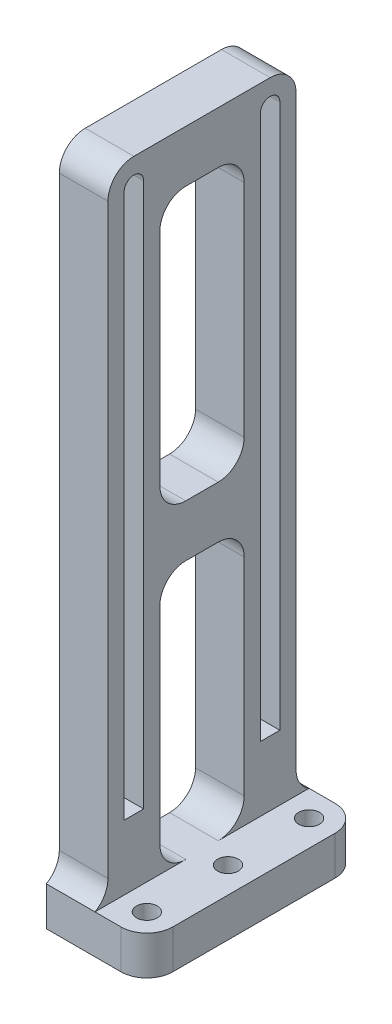
SolidWorks part; units mm, degrees
ref_plane "Front Plane" through (0, 0, 0) normal (0, 0, 1) x (1, 0, 0)
ref_plane "Top Plane" through (0, 0, 0) normal (0, 1, 0) x (1, 0, 0)
ref_plane "Right Plane" through (0, 0, 0) normal (1, 0, 0) x (0, 0, -1)
sketch "Sketch1" plane through (0, 0, 0) normal (0, 1, 0) x (1, 0, 0)
  line L0 (0, -12.5) -> (0, 12.5) construction
  line L1 (-4, -12.5) -> (-4, 12.5)
  line L2 (4, -12.5) -> (4, 12.5)
  line L3 (0, 16.5) -> (-4, 16.5)
  line L4 (-4, 16.5) -> (-4, 12.5)
  line L5 (-4, -12.5) -> (-4, -16.5)
  line L6 (-4, -16.5) -> (0, -16.5)
  arc A0 (-4, -12.5) -> (4, -12.5) centre (0, -12.5) ccw
  arc A1 (4, 12.5) -> (-4, 12.5) centre (0, 12.5) ccw
  circle A2 centre (0, -12.5) radius 1.6
  circle A3 centre (0, 0) radius 1.6
  circle A4 centre (0, 12.5) radius 1.6
  point P2 (0, 0)
  dimension "D2" = 3.2
  dimension "D1" = 25
  dimension "D3" = 8
extrude "Boss-Extrude1" add sketch "Sketch1" along normal blind 6
sketch "Sketch2" plane through (-4, 0, 0) normal (-1, 0, 0) x (0, 0, 1)
  line L0 (0, 0) -> (0, 99.754) construction
  line L1 (-16.5, 0) -> (16.5, 0) construction
  line L2 (0, 49.877) -> (-10.5, 49.877) construction
  line L3 (-10.5, -0.123) -> (-10.5, 99.877) construction
  line L4 (-14.5, -0.123) -> (-14.5, 99.877)
  line L5 (-6.5, -0.123) -> (-6.5, 99.877)
  line L6 (10.5, 99.877) -> (-10.5, 99.877) construction
  line L7 (-12, -0.123) -> (-12, 99.877)
  line L8 (-9, -0.123) -> (-9, 99.877)
  line L9 (10.5, 95.877) -> (-10.5, 95.877)
  line L10 (10.5, 49.877) -> (-10.5, 49.877) construction
  line L11 (9, -0.123) -> (9, 99.877)
  line L12 (12, -0.123) -> (12, 99.877)
  line L13 (10.5, -0.123) -> (10.5, 99.877) construction
  line L14 (14.5, -0.123) -> (14.5, 99.877)
  line L15 (6.5, -0.123) -> (6.5, 99.877)
  line L16 (10.5, 103.877) -> (-10.5, 103.877)
  line L17 (10.5, 45.877) -> (-10.5, 45.877)
  line L18 (-16.5, 0) -> (16.5, 0)
  line L19 (16.5, 0) -> (16.5, 6)
  line L20 (16.5, 6) -> (-16.5, 6)
  line L21 (-16.5, 6) -> (-16.5, 0)
  line L22 (-16.5, 0) -> (16.5, 0)
  line L23 (16.5, 0) -> (16.5, 6)
  line L24 (16.5, 6) -> (-16.5, 6)
  line L25 (-16.5, 6) -> (-16.5, 0)
  line L26 (10.5, 53.877) -> (-10.5, 53.877)
  line L27 (-12, 16) -> (-9, 16)
  line L28 (12, 16) -> (9, 16)
  arc A0 (-14.5, -0.123) -> (-6.5, -0.123) centre (-10.5, -0.123) ccw
  arc A1 (-6.5, 99.877) -> (-14.5, 99.877) centre (-10.5, 99.877) ccw
  arc A2 (-9, 99.877) -> (-12, 99.877) centre (-10.5, 99.877) ccw
  arc A3 (-12, -0.123) -> (-9, -0.123) centre (-10.5, -0.123) ccw
  arc A4 (9, 99.877) -> (12, 99.877) centre (10.5, 99.877) cw
  arc A5 (12, -0.123) -> (9, -0.123) centre (10.5, -0.123) cw
  arc A6 (14.5, -0.123) -> (6.5, -0.123) centre (10.5, -0.123) cw
  arc A7 (6.5, 99.877) -> (14.5, 99.877) centre (10.5, 99.877) cw
  arc A8 (10.5, 95.877) -> (10.5, 103.877) centre (10.5, 99.877) ccw
  arc A9 (-10.5, 103.877) -> (-10.5, 95.877) centre (-10.5, 99.877) ccw
  arc A10 (10.5, 45.877) -> (10.5, 53.877) centre (10.5, 49.877) ccw
  arc A11 (-10.5, 53.877) -> (-10.5, 45.877) centre (-10.5, 49.877) ccw
  point P8 (-10.5, 49.877)
  point P24 (0, 99.877)
  point P27 (10.5, 49.877)
  point P41 (0, 49.877)
  point P50 (-9.9307, 49.877)
  line M8 (-16.5, 0) -> (16.5, 0)
  line M9 (16.5, 0) -> (16.5, 6)
  line M10 (16.5, 6) -> (-16.5, 6)
  line M11 (-16.5, 6) -> (-16.5, 0)
  dimension "D1" = 8
  dimension "D3" = 3
  dimension "D4" = 100
  dimension "D6" = 10
  dimension "D7" = 21
  dimension "D2" = 2.5
  dimension "D5" = 0
extrude "Boss-Extrude2" add sketch "Sketch2" along normal blind 7.5 contours A10 L14 A8 L12 | L26 L11 L9 L15 | L12 A8 A7 L15 L9 L11 A4 | L15 A7 L16 A1 L5 L9 | A1 A9 L7 A2 L8 L9 L5 | A11 L7 A9 L4 | L26 L5 L9 L8 | L11 L26 L15 L17 | A10 L12 | L5 L26 L8 L17 | L7 A11 | A11 L4 L7 M10 | A10 L12 L14 M10 | L11 L17 L15 M10 | L14 L12 M8 M10 | L15 L11 M8 M10 | L8 L5 M8 M10 | L7 L4 M8 M10 | L5 L17 L8 M10 | L15 L5 M8 M10 | L4 M8 M10 M11 | L8 L7 M8 M10 | L14 M8 M9 M10 | L12 L11 M8 M10 | L15 L26 L5 L17 | L27 L7 L8 M10 | L12 L28 L11 M10
fillet "Fillet3" radius 4 4 edges at (-7.75, 6, 14.5) (-7.75, 6, 6.5) (-7.75, 6, -6.5) (-7.75, 6, -14.5)
fillet "Fillet4" radius 4 6 edges at (-7.75, 95.877, -6.5) (-7.75, 95.877, 6.5) (-7.75, 45.877, -6.5) (-7.75, 53.877, -6.5) (-7.75, 53.877, 6.5) (-7.75, 45.877, 6.5)
